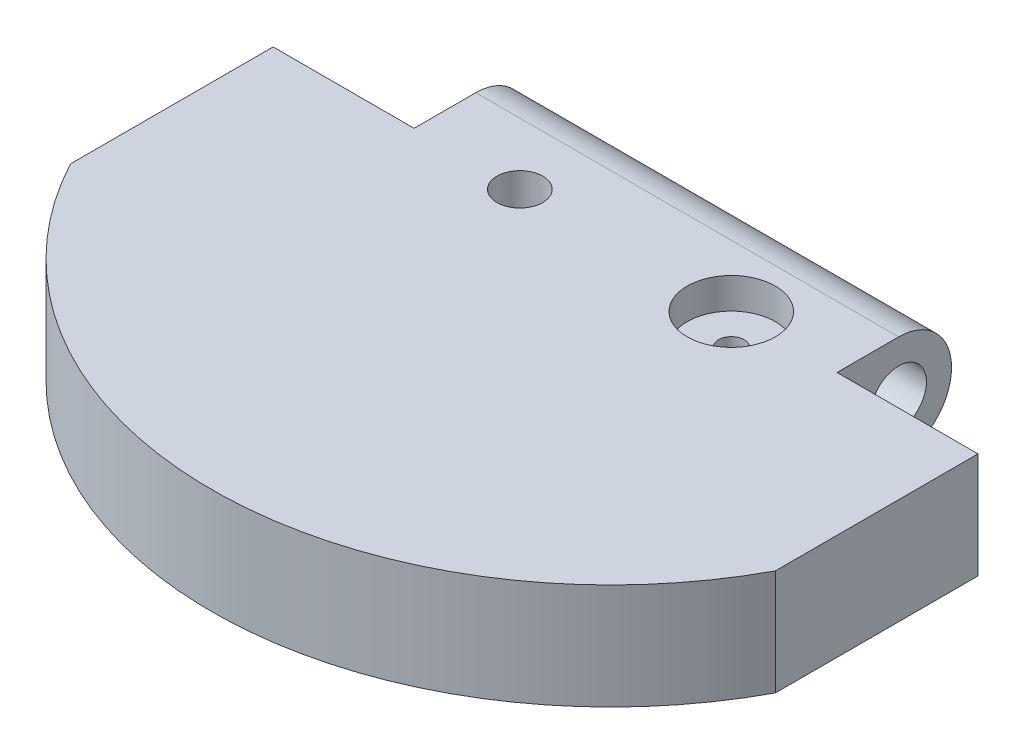
SolidWorks part; units mm, degrees
ref_plane "Front Plane" through (0, 0, 0) normal (0, 0, 1) x (1, 0, 0)
ref_plane "Top Plane" through (0, 0, 0) normal (0, 1, 0) x (1, 0, 0)
ref_plane "Right Plane" through (0, 0, 0) normal (1, 0, 0) x (0, 0, -1)
sketch "Sketch1" plane through (0, 0, 0) normal (0, 1, 0) x (1, 0, 0)
  line L1 (-40, -30) -> (40, -30)
  line L2 (-40, -30) -> (-40, 30)
  line L3 (-40, 30) -> (40, 30)
  line L4 (40, -30) -> (40, 30)
  line L5 (-40, -30) -> (40, 30) construction
  line L6 (-40, 30) -> (40, -30) construction
  line L7 (-24, 30) -> (-40, 30)
  line L8 (-24, 30) -> (-24, 17)
  line L9 (-24, 17) -> (-40, 17)
  line L10 (-40, 30) -> (-40, 17)
  line L11 (24, 30) -> (40, 30)
  line L12 (24, 30) -> (24, 17)
  line L13 (24, 17) -> (40, 17)
  line L14 (40, 30) -> (40, 17)
  arc A0 (-40, -6) -> (40, -6) centre (0, 15.3333) ccw
  point P0 (0, 0)
  dimension "D1" = 80
  dimension "D2" = 60
  dimension "D3" = 48
  dimension "D4" = 13
  dimension "D5" = 13
  dimension "D6" = 24
  dimension "D7" = 24
extrude "Boss-Extrude1" add sketch "Sketch1" along normal blind 12 contours A0 L4 L13 L12 L3 L8 L9 L2 region at (0, 0, -0.8069)
fillet "Fillet1" radius 6 2 edges at (0, 0, -30) (0, 12, -30)
sketch "Sketch2" plane through (-24, 0, 0) normal (-1, 0, 0) x (0, 0, 1)
  circle A0 centre (-24, 6) radius 3.15
  dimension "D1" = 6.3
extrude "Cut-Extrude1" cut sketch "Sketch2" against normal blind 70 contours A0
sketch "Sketch3" plane through (0, 12, 0) normal (0, 1, 0) x (1, 0, 0)
  line L0 (-24, 17) -> (0, 17) construction
  line L3 (0, 17) -> (24, 17) construction
  circle A0 centre (-12, 17) radius 1.45
  circle A1 centre (12, 17) radius 1.45
  circle A2 centre (-12, 17) radius 2.6
  circle A3 centre (12, 17) radius 2.6
  circle A4 centre (12, 17) radius 5
  circle A5 centre (-12, 17) radius 5
  dimension "D1" = 2.9
  dimension "D2" = 2.9
  dimension "D3" = 5.2
  dimension "D4" = 5.2
  dimension "D5" = 10
  dimension "D6" = 10
extrude "Cut-Extrude2" cut sketch "Sketch3" along normal blind 3.5 from surface contours A5 starting at face at (0, 0, -10)
extrude "Cut-Extrude3" cut sketch "Sketch3<3>" against normal blind 13.5 contours A0
sketch "Sketch3<3>" plane through (0, 12, 0) normal (0, 1, 0) x (1, 0, 0) same geometry as "Sketch3"
extrude "Cut-Extrude4" cut sketch "Sketch3<4>" against normal blind 4.4 contours A2
sketch "Sketch3<4>" plane through (0, 12, 0) normal (0, 1, 0) x (1, 0, 0) same geometry as "Sketch3"
extrude "Cut-Extrude5" cut sketch "Sketch3<5>" against normal blind 3.5 contours A4
sketch "Sketch3<5>" plane through (0, 12, 0) normal (0, 1, 0) x (1, 0, 0) same geometry as "Sketch3"
extrude "Cut-Extrude6" cut sketch "Sketch3<6>" against normal blind 18 contours A1
sketch "Sketch3<6>" plane through (0, 12, 0) normal (0, 1, 0) x (1, 0, 0) same geometry as "Sketch3"
extrude "Cut-Extrude7" cut sketch "Sketch3<7>" along normal blind 4.4 from surface contours A3 starting at face at (12, 0, -15.55)
sketch "Sketch3<7>" plane through (0, 12, 0) normal (0, 1, 0) x (1, 0, 0) same geometry as "Sketch3"
